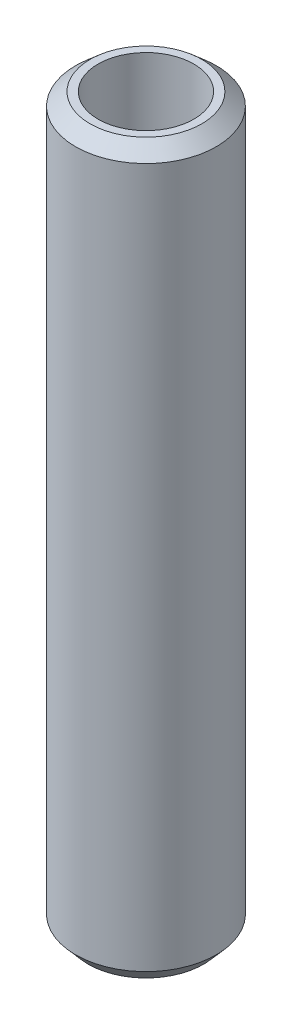
SolidWorks part; units mm, degrees
ref_plane "Front Plane" through (0, 0, 0) normal (0, 0, 1) x (1, 0, 0)
ref_plane "Top Plane" through (0, 0, 0) normal (0, 1, 0) x (1, 0, 0)
ref_plane "Right Plane" through (0, 0, 0) normal (1, 0, 0) x (0, 0, -1)
sketch "Sketch1" plane through (0, 0, 0) normal (0, 1, 0) x (1, 0, 0)
  circle A0 centre (0, 0) radius 27.5
  dimension "SHAFT_OD" = 55
extrude "Boss-Extrude1" add sketch "Sketch1" along normal blind 284.2174
sketch "Sketch2" plane through (0, 0, 0) normal (0, 1, 0) x (1, 0, 0)
  circle A0 centre (0, 0) radius 18.7162
  dimension "BORE_D" = 37.4324
extrude "Cut-Extrude1" cut sketch "Sketch2" along normal through all
chamfer "Chamfer1" distance 4.9354 angle 48.916 2 edges at (0, 284.2174, 27.5) (0, 0, 27.5) first distance on face at (0, 284.2174, 27.5) first distance on face at (0, 0, 18.7162)
